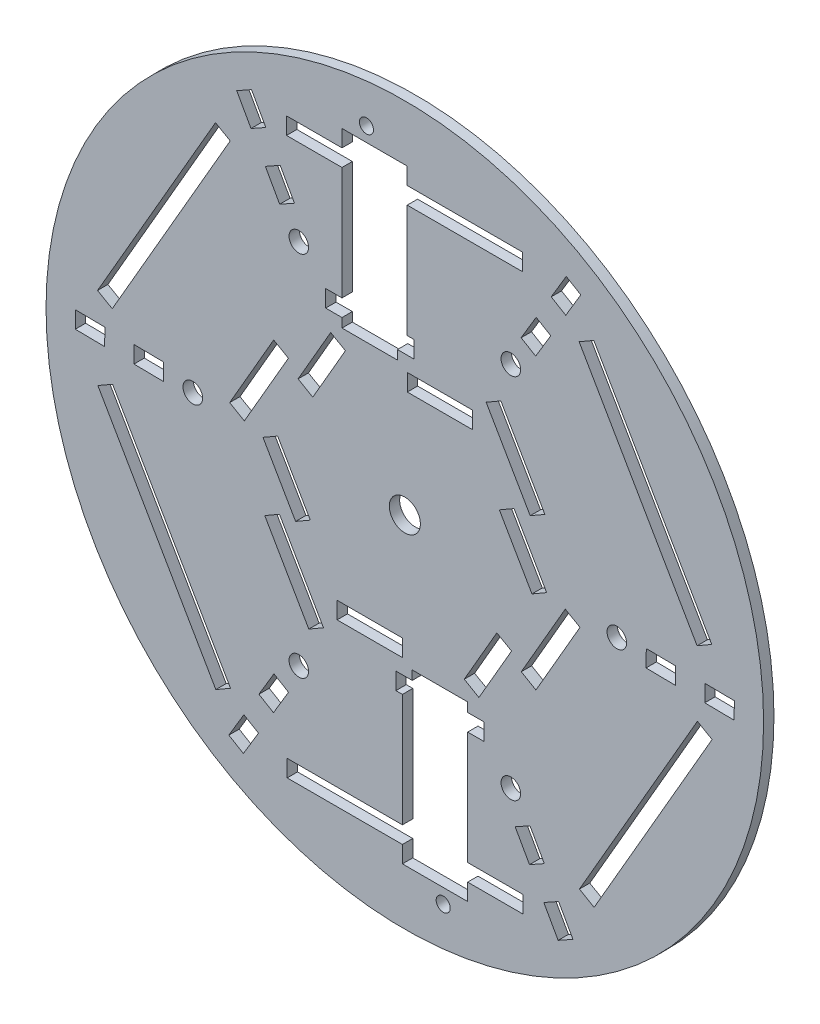
SolidWorks part; units mm, degrees
ref_plane "Front Plane" through (0, 0, 0) normal (0, 0, 1) x (1, 0, 0)
ref_plane "Top Plane" through (0, 0, 0) normal (0, 1, 0) x (1, 0, 0)
ref_plane "Right Plane" through (0, 0, 0) normal (1, 0, 0) x (0, 0, -1)
sketch "Sketch1" plane through (0, 0, 0) normal (0, 0, 1) x (1, 0, 0)
  line L0 (-4.7625, 0) -> (-4.7625, 42.8001) construction
  line L1 (-4.7625, 40) -> (-2.2625, 40)
  line L2 (-2.2625, 40) -> (-2.2625, 48)
  line L3 (-2.2625, 48) -> (0.7375, 48)
  line L4 (0.7375, 48) -> (0.7375, 93)
  line L5 (0.7375, 93) -> (-19.2625, 93)
  line L6 (-19.2625, 93) -> (-19.2625, 40)
  line L7 (-19.2625, 40) -> (-16.7625, 40)
  line L8 (-16.7625, 40) -> (-4.7625, 40)
  line L9 (-4.7625, 40) -> (-4.7625, 0)
  line L10 (4.7625, -40) -> (2.2625, -40)
  line L11 (2.2625, -40) -> (2.2625, -48)
  line L12 (2.2625, -48) -> (-0.7375, -48)
  line L13 (-0.7375, -48) -> (-0.7375, -93)
  line L14 (-0.7375, -93) -> (19.2625, -93)
  line L15 (19.2625, -93) -> (19.2625, -40)
  line L16 (19.2625, -40) -> (16.7625, -40)
  line L17 (16.7625, -40) -> (4.7625, -40)
  line L18 (-2.2625, 40) -> (2.2625, -40) construction
  circle A0 centre (0, 0) radius 110
  circle A1 centre (0, 0) radius 4.7625
  point P14 (-4.7625, 0)
  point P27 (0, 0)
  point P46 (0, 0)
  dimension "D5" = 9.525
  dimension "D11" = 220
  dimension "D1" = 17
  dimension "D2" = 12
  dimension "D3" = 53
  dimension "D4" = 45
  dimension "D6" = 20
  dimension "D7" = 40
  dimension "D8" = 2
extrude "Boss-Extrude1" add sketch "Sketch1" along normal mid plane 3.175 contours A0 A1 L8 L7 L6 L5 L4 L3 L2 L1 L17 L16 L15 L14 L13 L12 L11 L10 region at (-106.8887, 0, 0)
sketch "Sketch2" plane through (0, 0, 1.5875) normal (0, 0, 1) x (1, 0, 0)
  line L0 (-0.7375, -93) -> (19.2625, -93) construction
  line L2 (0, 0) -> (45.6639, 0) construction
  line L6 (11.7625, -99.5925) -> (11.7625, -101.88) construction
  line L12 (0, -53.2538) -> (0, -302.3208) construction
  line L13 (0, -1.7463) -> (0, 1.7463) construction
  line L14 (0, 0) -> (55, -95.2628) construction
  line L15 (0, 0) -> (-55, -95.2628) construction
  line L17 (19.2625, -93) -> (19.2625, -40) construction
  circle A2 centre (0, 0) radius 110 construction
  circle A3 centre (11.7625, -97.4387) radius 2.1538
  point P4 (11.7625, -95.285)
  dimension "D10" = 4.3075
  dimension "D2" = 2.2875
  dimension "D3" = 60
  dimension "D6" = 2.285
  dimension "D8" = 7.5
extrude "Cut-Extrude3" cut sketch "Sketch2" against normal through all
ref_axis "Axis1" through (0, 0, 1.7463) along (0, 0, -1)
pattern_circular "CirPattern1" count 2 over 360 about axis through (0, 0, 1.7463) along (0, 0, -1) of "Cut-Extrude3"
sketch "Sketch11" plane through (0, 0, 1.5875) normal (0, 0, 1) x (1, 0, 0)
  line L0 (-19.2625, 40) -> (-2.2625, 40) construction
  line L1 (-19.067, 33.025) -> (-38.134, 0) construction
  line L2 (-38.134, 0) -> (-19.067, -33.025) construction
  line L3 (-19.067, -33.025) -> (19.067, -33.025) construction
  line L4 (19.067, -33.025) -> (38.134, 0) construction
  line L5 (38.134, 0) -> (19.067, 33.025) construction
  line L6 (19.067, 33.025) -> (-19.067, 33.025) construction
  line L7 (-2.7375, -48) -> (24.2625, -48)
  line L8 (-2.7375, -42.8) -> (2.2625, -42.8)
  line L9 (-2.7375, -48) -> (-2.7375, -42.8)
  line L10 (2.2625, -42.8) -> (19.2625, -42.8)
  line L11 (24.2625, -42.8) -> (24.2625, -48)
  line L12 (2.2625, -48) -> (-0.7375, -48) construction
  line L13 (-42.938, -21.6293) -> (-29.438, -45.0119)
  line L14 (-20.7625, -33.025) -> (-16.7625, -33.025)
  line L15 (-16.7625, -33.025) -> (-4.7625, -33.025)
  line L16 (-20.7625, -38.225) -> (-20.7625, -33.025)
  line L17 (-20.7625, -38.225) -> (-0.7625, -38.225)
  line L18 (-4.7625, -33.025) -> (-0.7625, -33.025)
  line L19 (19.2625, -93) -> (19.2625, -40) construction
  line L20 (-0.7625, -33.025) -> (-0.7625, -38.225)
  line L21 (-42.938, -21.6293) -> (-38.4346, -19.0293)
  line L22 (-38.4346, -19.0293) -> (-24.9346, -42.4119)
  line L23 (-24.9346, -42.4119) -> (-29.438, -45.0119)
  line L24 (-38.9817, 1.4684) -> (-36.9817, -1.9957)
  line L25 (-36.9817, -1.9957) -> (-30.9817, -12.3881)
  line L26 (-43.4851, -1.1316) -> (-38.9817, 1.4684)
  line L27 (-43.4851, -1.1316) -> (-33.4851, -18.4522)
  line L28 (-38.134, 0) -> (-19.067, -33.025) construction
  line L29 (-40.2005, 26.3707) -> (-53.7005, 2.9881)
  line L30 (-40.2005, 26.3707) -> (-35.6971, 23.7707)
  line L31 (-35.6971, 23.7707) -> (-49.1971, 0.3881)
  line L32 (-49.1971, 0.3881) -> (-53.7005, 2.9881)
  line L33 (-30.9817, -12.3881) -> (-28.9817, -15.8522)
  line L34 (-28.9817, -15.8522) -> (-33.4851, -18.4522)
  line L35 (-18.2192, 34.4934) -> (-20.2192, 31.0293)
  line L36 (-20.2192, 31.0293) -> (-26.2192, 20.6369)
  line L37 (-19.067, 33.025) -> (-38.134, 0) construction
  line L38 (2.7375, 48) -> (-24.2625, 48)
  line L39 (2.7375, 48) -> (2.7375, 42.8)
  line L40 (2.7375, 42.8) -> (-24.2625, 42.8)
  line L41 (-24.2625, 42.8) -> (-24.2625, 48)
  line L42 (-22.7226, 37.0934) -> (-18.2192, 34.4934)
  line L43 (-22.7226, 37.0934) -> (-32.7226, 19.7728)
  line L44 (-26.2192, 20.6369) -> (-28.2192, 17.1728)
  line L45 (-28.2192, 17.1728) -> (-32.7226, 19.7728)
  line L46 (19.067, 33.025) -> (-19.067, 33.025) construction
  line L47 (42.938, 21.6293) -> (29.438, 45.0119)
  line L48 (42.938, 21.6293) -> (38.4346, 19.0293)
  line L49 (38.4346, 19.0293) -> (24.9346, 42.4119)
  line L50 (24.9346, 42.4119) -> (29.438, 45.0119)
  line L51 (20.7625, 33.025) -> (16.7625, 33.025)
  line L52 (16.7625, 33.025) -> (4.7625, 33.025)
  line L53 (20.7625, 38.225) -> (20.7625, 33.025)
  line L54 (20.7625, 38.225) -> (0.7625, 38.225)
  line L55 (38.134, 0) -> (19.067, 33.025) construction
  line L56 (40.2005, -26.3707) -> (53.7005, -2.9881)
  line L57 (40.2005, -26.3707) -> (35.6971, -23.7707)
  line L58 (35.6971, -23.7707) -> (49.1971, -0.3881)
  line L59 (49.1971, -0.3881) -> (53.7005, -2.9881)
  line L60 (4.7625, 33.025) -> (0.7625, 33.025)
  line L61 (0.7625, 33.025) -> (0.7625, 38.225)
  line L62 (38.9817, -1.4684) -> (36.9817, 1.9957)
  line L63 (36.9817, 1.9957) -> (30.9817, 12.3881)
  line L64 (19.067, -33.025) -> (38.134, 0) construction
  line L65 (19.2625, -42.8) -> (24.2625, -42.8)
  line L66 (2.2625, -40) -> (2.2625, -48) construction
  line L67 (-16.7625, 40) -> (-16.7625, 20.0418) construction
  line L68 (-4.7625, 40) -> (-4.7625, 20.0418) construction
  line L69 (-19.2625, 93) -> (-19.2625, 40) construction
  line L70 (43.4851, 1.1316) -> (38.9817, -1.4684)
  line L71 (22.7226, -37.0934) -> (32.7226, -19.7728) [skipped]
  line L72 (43.4851, 1.1316) -> (33.4851, 18.4522) [skipped]
  line L73 (-43.4851, -1.1316) -> (-33.4851, -18.4522) [skipped]
  line L74 (-22.7226, 37.0934) -> (-32.7226, 19.7728) [skipped]
  line L75 (20.7625, 38.225) -> (0.7625, 38.225) [skipped]
  line L76 (43.4851, 1.1316) -> (33.4851, 18.4522)
  line L77 (30.9817, 12.3881) -> (28.9817, 15.8522)
  line L78 (28.9817, 15.8522) -> (33.4851, 18.4522)
  line L79 (18.2192, -34.4934) -> (20.2192, -31.0293)
  line L80 (20.2192, -31.0293) -> (26.2192, -20.6369)
  line L81 (22.7226, -37.0934) -> (18.2192, -34.4934)
  line L82 (22.7226, -37.0934) -> (32.7226, -19.7728)
  line L83 (26.2192, -20.6369) -> (28.2192, -17.1728)
  line L84 (28.2192, -17.1728) -> (32.7226, -19.7728)
  line L85 (36.2625, -82.6394) -> (-36.0675, -82.6394)
  line L86 (-36.0675, -82.6394) -> (-36.0675, -87.8394)
  line L87 (-36.0675, -87.8394) -> (36.2625, -87.8394)
  line L88 (36.2625, -87.8394) -> (36.2625, -82.6394)
  line L89 (19.2625, -93) -> (19.2625, -40) construction
  line L90 (-53.4366, -72.7239) -> (-89.6016, -10.0843)
  line L91 (-89.6016, -10.0843) -> (-94.1049, -12.6843)
  line L92 (-94.1049, -12.6843) -> (-57.9399, -75.3239)
  line L93 (-57.9399, -75.3239) -> (-53.4366, -72.7239)
  line L94 (-89.6991, 9.9154) -> (-53.5341, 72.5551)
  line L95 (-53.5341, 72.5551) -> (-58.0374, 75.1551)
  line L96 (-58.0374, 75.1551) -> (-94.2024, 12.5154)
  line L97 (-94.2024, 12.5154) -> (-89.6991, 9.9154)
  line L98 (-36.2625, 82.6394) -> (36.0675, 82.6394)
  line L99 (36.0675, 82.6394) -> (36.0675, 87.8394)
  line L100 (36.0675, 87.8394) -> (-36.2625, 87.8394)
  line L101 (-36.2625, 87.8394) -> (-36.2625, 82.6394)
  line L102 (53.4366, 72.7239) -> (89.6016, 10.0843)
  line L103 (89.6016, 10.0843) -> (94.1049, 12.6843)
  line L104 (94.1049, 12.6843) -> (57.9399, 75.3239)
  line L105 (57.9399, 75.3239) -> (53.4366, 72.7239)
  line L106 (89.6991, -9.9154) -> (53.5341, -72.5551)
  line L107 (53.5341, -72.5551) -> (58.0374, -75.1551)
  line L108 (58.0374, -75.1551) -> (94.2024, -12.5154)
  line L109 (94.2024, -12.5154) -> (89.6991, -9.9154)
  line L111 (-42.501, -71.2928) -> (-47.1096, -79.0234) construction
  line L112 (-42.501, -71.2928) -> (-44.7343, -69.9614)
  line L113 (-44.7343, -69.9614) -> (-40.1257, -62.2309)
  line L114 (-40.1257, -62.2309) -> (-35.6592, -64.8936)
  line L115 (-35.6592, -64.8936) -> (-40.2677, -72.6242)
  line L116 (-40.2677, -72.6242) -> (-42.501, -71.2928)
  line L117 (-47.1096, -79.0234) -> (-49.3428, -77.692)
  line L118 (-49.3428, -77.692) -> (-53.9514, -85.4225)
  line L119 (-53.9514, -85.4225) -> (-49.4848, -88.0853)
  line L120 (-49.4848, -88.0853) -> (-44.8763, -80.3547)
  line L121 (-44.8763, -80.3547) -> (-47.1096, -79.0234)
  line L122 (-51.7181, -86.7539) -> (-56.3266, -94.4844) construction
  line L123 (-91.991, 1.2864) -> (-91.9547, 3.8861)
  line L124 (-91.9547, 3.8861) -> (-100.9538, 4.012)
  line L125 (-100.9538, 4.012) -> (-101.0265, -1.1875)
  line L126 (-101.0265, -1.1875) -> (-92.0274, -1.3134)
  line L127 (-92.0274, -1.3134) -> (-91.991, 1.2864)
  line L128 (-83.0282, -1.4392) -> (-82.9919, 1.1606)
  line L129 (-82.9919, 1.1606) -> (-82.9555, 3.7603)
  line L130 (-82.9555, 3.7603) -> (-73.9564, 3.6345)
  line L131 (-73.9564, 3.6345) -> (-74.0291, -1.565)
  line L132 (-74.0291, -1.565) -> (-83.0282, -1.4392)
  line L133 (-44.8815, 80.3097) -> (-42.6118, 81.5781)
  line L134 (-42.6118, 81.5781) -> (-47.0024, 89.4345)
  line L135 (-47.0024, 89.4345) -> (-51.5417, 86.8977)
  line L136 (32.5, -56.2917) -> (0, 0) construction
  line L137 (0, -1.7463) -> (0, 1.7463) construction
  line L138 (-51.5417, 86.8977) -> (-47.1511, 79.0414)
  line L139 (-47.1511, 79.0414) -> (-44.8815, 80.3097)
  line L140 (-42.7605, 71.185) -> (-40.4909, 72.4534)
  line L141 (-40.4909, 72.4534) -> (-38.2213, 73.7217)
  line L142 (-38.2213, 73.7217) -> (-33.8307, 65.8654)
  line L143 (-33.8307, 65.8654) -> (-38.3699, 63.3286)
  line L144 (-38.3699, 63.3286) -> (-42.7605, 71.185)
  line L145 (47.1096, 79.0234) -> (49.3428, 77.692)
  line L146 (49.3428, 77.692) -> (53.9514, 85.4225)
  line L147 (53.9514, 85.4225) -> (49.4848, 88.0853)
  line L148 (49.4848, 88.0853) -> (44.8763, 80.3547)
  line L149 (44.8763, 80.3547) -> (47.1096, 79.0234)
  line L150 (40.2677, 72.6242) -> (42.501, 71.2928)
  line L151 (42.501, 71.2928) -> (44.7343, 69.9614)
  line L152 (44.7343, 69.9614) -> (40.1257, 62.2309)
  line L153 (40.1257, 62.2309) -> (35.6592, 64.8936)
  line L154 (35.6592, 64.8936) -> (40.2677, 72.6242)
  line L155 (91.991, -1.2864) -> (91.9547, -3.8861)
  line L156 (91.9547, -3.8861) -> (100.9538, -4.012)
  line L157 (100.9538, -4.012) -> (101.0265, 1.1875)
  line L158 (101.0265, 1.1875) -> (92.0274, 1.3134)
  line L159 (92.0274, 1.3134) -> (91.991, -1.2864)
  line L160 (83.0282, 1.4392) -> (82.9919, -1.1606)
  line L161 (82.9919, -1.1606) -> (82.9555, -3.7603)
  line L162 (82.9555, -3.7603) -> (73.9564, -3.6345)
  line L163 (73.9564, -3.6345) -> (74.0291, 1.565)
  line L164 (74.0291, 1.565) -> (83.0282, 1.4392)
  line L165 (44.8815, -80.3097) -> (42.6118, -81.5781)
  line L166 (42.6118, -81.5781) -> (47.0024, -89.4345)
  line L167 (47.0024, -89.4345) -> (51.5417, -86.8977)
  line L168 (51.5417, -86.8977) -> (47.1511, -79.0414)
  line L169 (47.1511, -79.0414) -> (44.8815, -80.3097)
  line L170 (42.7605, -71.185) -> (40.4909, -72.4534)
  line L171 (40.4909, -72.4534) -> (38.2213, -73.7217)
  line L172 (38.2213, -73.7217) -> (33.8307, -65.8654)
  line L173 (33.8307, -65.8654) -> (38.3699, -63.3286)
  line L174 (38.3699, -63.3286) -> (42.7605, -71.185)
  circle A0 centre (0, 0) radius 33.025 construction
  circle A1 centre (32.5, -56.2917) radius 3
  circle A2 centre (-32.5, -56.2917) radius 3
  circle A3 centre (-65, 0) radius 3
  circle A4 centre (-32.5, 56.2917) radius 3
  circle A5 centre (32.5, 56.2917) radius 3
  circle A6 centre (65, 0) radius 3
  circle A7 centre (0, 0) radius 110 construction
  point P72 (0, 0)
  point P109 (0, 0)
  point P112 (19.2625, -82.6394)
  point P123 (0, 0)
  point P133 (-61.9366, -58.0015)
  point P138 (-81.1991, 24.6379)
  point P143 (-19.2625, 82.6394)
  point P148 (61.9366, 58.0015)
  point P153 (81.1991, -24.6379)
  point P156 (0, 0)
  point P185 (0, 0)
  point P225 (0, 0)
  dimension "D1" = 66.05
  dimension "D11" = 6
  dimension "D2" = 5
  dimension "D3" = 2.5
  dimension "D4" = 5.2
  dimension "D5" = 4
  dimension "D6" = 20
  dimension "D7" = 6
  dimension "D8" = 2.5
  dimension "D9" = 5.2
  dimension "D13" = 65
  dimension "D14" = 30
  dimension "D15" = 72.33
  dimension "D16" = 5.2
  dimension "D17" = 17
  dimension "D19" = 20
  dimension "D20" = 9
  dimension "D21" = 9
  dimension "D22" = 5.2
  dimension "D24" = 8.6603
  dimension "D10" = 6
  dimension "D12" = 6
  dimension "D18" = 6
  dimension "D23" = 6
extrude "Cut-Extrude24" cut sketch "Sketch11" against normal mid plane 10
